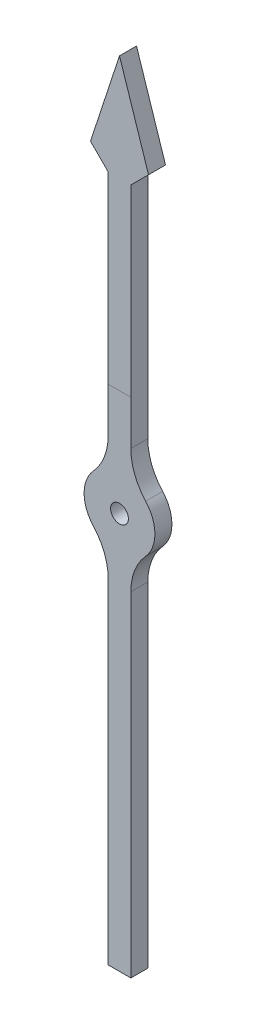
SolidWorks part; units mm, degrees
material "Acrylic (Medium-high impact)"
ref_plane "Front Plane" through (0, 0, 0) normal (0, 0, 1) x (1, 0, 0)
ref_plane "Top Plane" through (0, 0, 0) normal (0, 1, 0) x (1, 0, 0)
ref_plane "Right Plane" through (0, 0, 0) normal (1, 0, 0) x (0, 0, -1)
sketch "Sketch1" plane through (0, 0, 0) normal (0, 0, 1) x (1, 0, 0)
  line L0 (0, 0) -> (0, 17.78) construction
  line L1 (0, 0) -> (0, -17.78) construction
  line L2 (-0.508, 13.0175) -> (-1.3017, 13.8112)
  line L3 (-0.508, -1.504) -> (-0.508, -17.78)
  line L4 (0.508, -1.504) -> (0.508, -17.78)
  line L5 (-0.508, 0) -> (-0.508, -17.78) construction
  line L6 (0.508, 0) -> (0.508, -17.78) construction
  line L7 (0.508, 1.504) -> (0.508, 13.0175)
  line L8 (-0.508, 1.504) -> (-0.508, 13.0175)
  line L9 (-0.508, 0) -> (-0.508, 17.78) construction
  line L10 (0.508, 0) -> (0.508, 17.78) construction
  line L11 (-1.3017, 13.8112) -> (0, 17.78)
  line L12 (-0.508, -17.78) -> (0.508, -17.78)
  line L13 (1.3017, 13.8112) -> (0, 17.78)
  line L14 (0.508, 13.0175) -> (1.3017, 13.8112)
  circle A0 centre (0, 0) radius 0.4
  arc A1 (0.508, -1.504) -> (0.508, 1.504) centre (0, 0) ccw
  arc A3 (-0.508, 1.504) -> (-0.508, -1.504) centre (0, 0) ccw
  dimension "D1" = 0.8
  dimension "D2" = 3.175
  dimension "D5" = 0.508
  dimension "D3" = 17.78
  dimension "D4" = 17.78
  dimension "D9" = 4.7625
  dimension "D7" = 0.7937
  dimension "D10" = 3.9688
  dimension "D6" = 0.508
  dimension "D8" = 0.508
extrude "Boss-Extrude1" add sketch "Sketch1" along normal blind 0.762
sketch "Sketch2" plane through (0, 0, 0.762) normal (0, 0, 1) x (1, 0, 0)
  line L0 (-0.508, 4.7752) -> (0.508, 4.7752)
  line L1 (-0.508, 13.0175) -> (-0.508, 1.504) construction
  line L2 (0.508, 1.504) -> (0.508, 13.0175) construction
  dimension "D1" = 4.7752
split line "Split Line1"
fillet "Fillet1" radius 2.54 4 edges at (-0.508, -1.504, 0.381) (0.508, -1.504, 0.381) (0.508, 1.504, 0.381) (-0.508, 1.504, 0.381)
